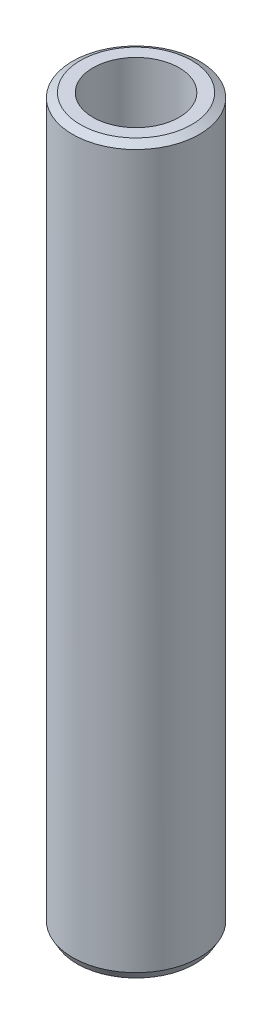
SolidWorks part; units mm, degrees
ref_plane "Front Plane" through (0, 0, 0) normal (0, 0, 1) x (1, 0, 0)
ref_plane "Top Plane" through (0, 0, 0) normal (0, 1, 0) x (1, 0, 0)
ref_plane "Right Plane" through (0, 0, 0) normal (1, 0, 0) x (0, 0, -1)
sketch "Sketch1" plane through (0, 0, 0) normal (0, 1, 0) x (1, 0, 0)
  circle A0 centre (0, 0) radius 52.5
  dimension "SHAFT_OD" = 105
extrude "Boss-Extrude1" add sketch "Sketch1" along normal blind 600
sketch "Sketch2" plane through (0, 0, 0) normal (0, 1, 0) x (1, 0, 0)
  circle A0 centre (0, 0) radius 35.6018
  dimension "BORE_D" = 71.2036
extrude "Cut-Extrude1" cut sketch "Sketch2" along normal through all
chamfer "Chamfer1" distance 3.7322 angle 60 2 edges at (0, 600, 52.5) (0, 0, 52.5) first distance on face at (0, 600, 52.5) first distance on face at (0, 0, 35.6018)
